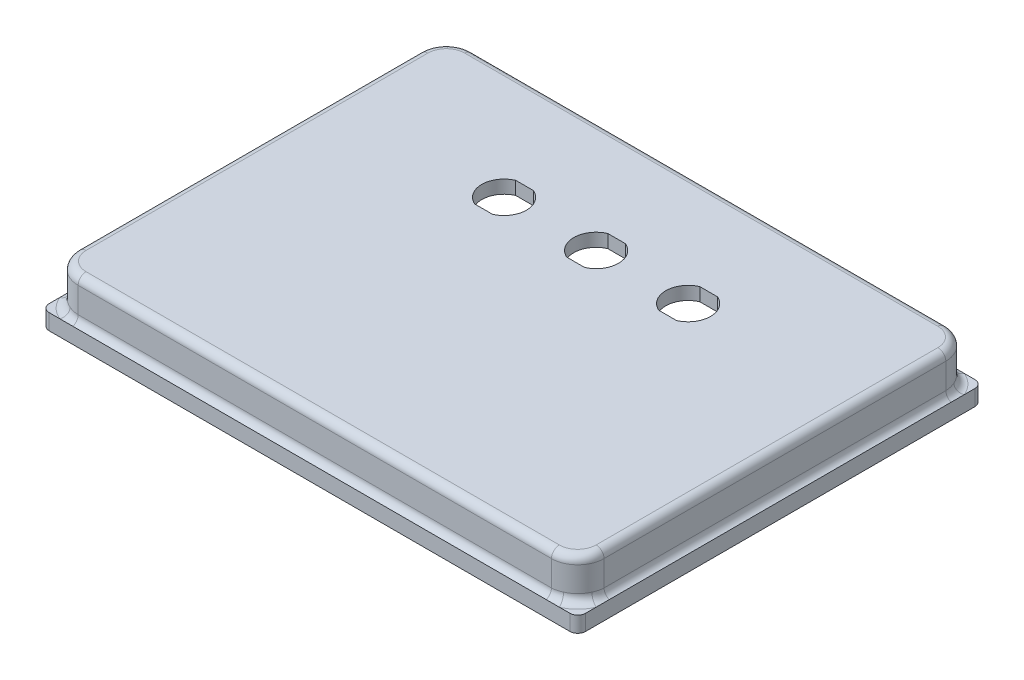
SolidWorks part; units mm, degrees
ref_plane "Front Plane" through (0, 0, 0) normal (0, 0, 1) x (1, 0, 0)
ref_plane "Top Plane" through (0, 0, 0) normal (0, 1, 0) x (1, 0, 0)
ref_plane "Right Plane" through (0, 0, 0) normal (1, 0, 0) x (0, 0, -1)
sketch "Sketch1" plane through (0, 0, 0) normal (0, 1, 0) x (1, 0, 0)
  line L0 (5.25, 5.25) -> (5.25, 144.75)
  line L1 (0, 0) -> (200, 0)
  line L2 (0, 0) -> (0, 150)
  line L3 (0, 150) -> (200, 150)
  line L4 (200, 0) -> (200, 150)
  line L5 (5.25, 144.75) -> (194.75, 144.75)
  line L6 (194.75, 5.25) -> (194.75, 144.75)
  line L7 (5.25, 5.25) -> (194.75, 5.25)
  line L8 (0, 150) -> (18.9, 131.1) construction
  line L9 (5.25, 144.75) -> (18.9, 144.75) construction
  line L10 (5.25, 144.75) -> (5.25, 131.1) construction
  line L11 (5.25, 131.1) -> (18.9, 131.1) construction
  line L12 (18.9, 144.75) -> (18.9, 131.1) construction
  line L13 (194.75, 144.75) -> (181.1, 144.75) construction
  line L14 (194.75, 144.75) -> (194.75, 131.1) construction
  line L15 (194.75, 131.1) -> (181.1, 131.1) construction
  line L16 (181.1, 144.75) -> (181.1, 131.1) construction
  line L17 (5.25, 5.25) -> (18.9, 5.25) construction
  line L18 (5.25, 5.25) -> (5.25, 18.9) construction
  line L19 (5.25, 18.9) -> (18.9, 18.9) construction
  line L20 (18.9, 5.25) -> (18.9, 18.9) construction
  line L21 (18.9, 144.75) -> (18.9, 140.1538)
  line L22 (100, 150) -> (100, 0) construction
  line L23 (9.8462, 131.1) -> (5.25, 131.1)
  line L24 (190.1538, 131.1) -> (194.75, 131.1)
  line L25 (200, 75) -> (0, 75) construction
  line L26 (181.1, 144.75) -> (181.1, 140.1538)
  line L27 (0, 0) -> (18.9, 18.9) construction
  line L28 (5.25, 18.9) -> (9.8462, 18.9)
  line L29 (18.9, 9.8462) -> (18.9, 5.25)
  line L30 (181.1, 9.8462) -> (181.1, 5.25)
  line L31 (194.75, 18.9) -> (190.1538, 18.9)
  circle A0 centre (9.8462, 140.1538) radius 6.5 construction
  circle A1 centre (9.8462, 140.1538) radius 3
  arc A2 (9.8462, 131.1) -> (18.9, 140.1538) centre (9.8462, 140.1538) ccw
  circle A3 centre (190.1538, 140.1538) radius 3
  arc A4 (190.1538, 131.1) -> (181.1, 140.1538) centre (190.1538, 140.1538) cw
  circle A5 centre (9.8462, 9.8462) radius 6.5 construction
  circle A6 centre (9.8462, 9.8462) radius 3
  arc A7 (18.9, 9.8462) -> (9.8462, 18.9) centre (9.8462, 9.8462) ccw
  arc A8 (181.1, 9.8462) -> (190.1538, 18.9) centre (190.1538, 9.8462) cw
  circle A9 centre (190.1538, 140.1538) radius 3
  circle A10 centre (190.1538, 9.8462) radius 3
  dimension "D6" = 13
  dimension "D7" = 6
  dimension "D8" = 13
  dimension "D1" = 150
  dimension "D2" = 200
  dimension "D4" = 162.2
  dimension "D5" = 112.2
  dimension "D3" = 5.25
extrude "Boss-Extrude1" add sketch "Sketch1" along normal blind 15.5 contours L1 L4 L3 L2 L7 L0 L5 L6 | L29 A7 L28 L0 L7 A6 | L23 A2 L21 L5 L0 A1 | A4 L24 L6 L5 L26 A3 | A8 L30 L7 L6 L31 A10 region at (5.443, 0, -12.075) region at (5.443, 0, -137.925) region at (181.293, 0, -7.5481) region at (187.925, 0, -144.557) region at (2.5, 0, -75)
sketch "Sketch2" plane through (0, 15.5, 0) normal (0, 1, 0) x (1, 0, 0)
  line L1 (0, 150) -> (200, 150)
  line L2 (0, 150) -> (0, 0)
  line L3 (0, 0) -> (200, 0)
  line L4 (200, 150) -> (200, 0)
extrude "Boss-Extrude2" add sketch "Sketch2" along normal blind 5
sketch "Sketch3" plane through (0, 0, 0) normal (0, -1, 0) x (1, 0, 0)
  line L14 (18.9, -5.25) -> (181.1, -5.25) construction
  line L15 (5.25, -5.25) -> (194.75, -5.25)
  line L16 (5.25, -5.25) -> (5.25, -144.75)
  line L17 (5.25, -144.75) -> (194.75, -144.75)
  line L18 (202, -152) -> (202, 2)
  line L19 (-2, -152) -> (202, -152)
  line L20 (-2, 2) -> (-2, -152)
  line L21 (202, 2) -> (-2, 2)
  line L22 (202, -152) -> (202, 2)
  line L23 (-2, -152) -> (202, -152)
  line L24 (-2, 2) -> (-2, -152)
  line L25 (202, 2) -> (-2, 2)
  line L26 (194.75, -5.25) -> (194.75, -144.75)
  line L27 (5.25, -18.9) -> (5.25, -131.1) construction
  line L28 (18.9, -144.75) -> (181.1, -144.75) construction
  line L29 (194.75, -18.9) -> (194.75, -131.1) construction
  dimension "D1" = 2
extrude "Boss-Extrude3" add sketch "Sketch3" against normal blind 5
sketch "Sketch4" plane through (0, 0, 0) normal (0, -1, 0) x (1, 0, 0)
  line L0 (0, 0) -> (0, -150)
  line L1 (-2, 2) -> (202, 2)
  line L2 (-2, 2) -> (-2, -152)
  line L3 (-2, -152) -> (202, -152)
  line L4 (202, 2) -> (202, -152)
  line L5 (0, -150) -> (200, -150)
  line L6 (200, 0) -> (200, -150)
  line L7 (0, 0) -> (200, 0)
  dimension "D1" = 2
extrude "Boss-Extrude4" add sketch "Sketch4" along normal blind 1
fillet "Fillet1" radius 10 4 edges at (200, 12.75, -150) (200, 12.75, 0) (0, 12.75, -150) (0, 12.75, 0)
fillet "Fillet2" radius 3 15 edges at (197.0711, 5, -2.9289) (197.0711, 5, -147.0711) (2.9289, 5, -147.0711) (197.0711, 20.5, -2.9289) (100, 20.5, 0) (2.9289, 20.5, -2.9289) (0, 20.5, -75) (2.9289, 20.5, -147.0711) (100, 20.5, -150) (197.0711, 20.5, -147.0711) (200, 20.5, -75) (2.9289, 5, -2.9289) (-2, 2, 2) (202, 2, 2) (202, 2, -152)
sketch "Sketch6" plane through (0, 20.5, 0) normal (0, 1, 0) x (1, 0, 0)
  line L0 (3, 107) -> (197, 107) construction
  line L1 (3, 140) -> (3, 10) construction
  line L2 (197, 10) -> (197, 140) construction
  line L3 (100, 107) -> (100, 147) construction
  line L4 (190, 147) -> (10, 147) construction
  line L5 (96.6221, 114.8) -> (103.3779, 114.8)
  line L6 (103.3779, 114.8) -> (103.3779, 99.2) construction
  line L7 (103.3779, 99.2) -> (96.6221, 99.2)
  line L8 (131.6221, 114.8) -> (138.3779, 114.8)
  line L9 (138.3779, 99.2) -> (131.6221, 99.2)
  line L10 (68.3779, 99.2) -> (61.6221, 99.2)
  line L11 (61.6221, 114.8) -> (68.3779, 114.8)
  circle A0 centre (100, 107) radius 12.5 construction
  circle A1 centre (100, 107) radius 8.5
  circle A2 centre (135, 107) radius 8.5
  circle A3 centre (65, 107) radius 8.5
  dimension "D1" = 17
  dimension "D2" = 25
  dimension "D7" = 35
  dimension "D8" = 35
  dimension "D3" = 40
  dimension "D4" = 15.6
  dimension "D5" = 2
  dimension "D6" = 2
extrude "Cut-Extrude1" cut sketch "Sketch6" against normal blind 10 contours L10 A3 L11 | L7 A1 L5 | L9 A2 L8 region at (100, 20.5, -107) region at (135, 20.5, -107) region at (65, 20.5, -107)
